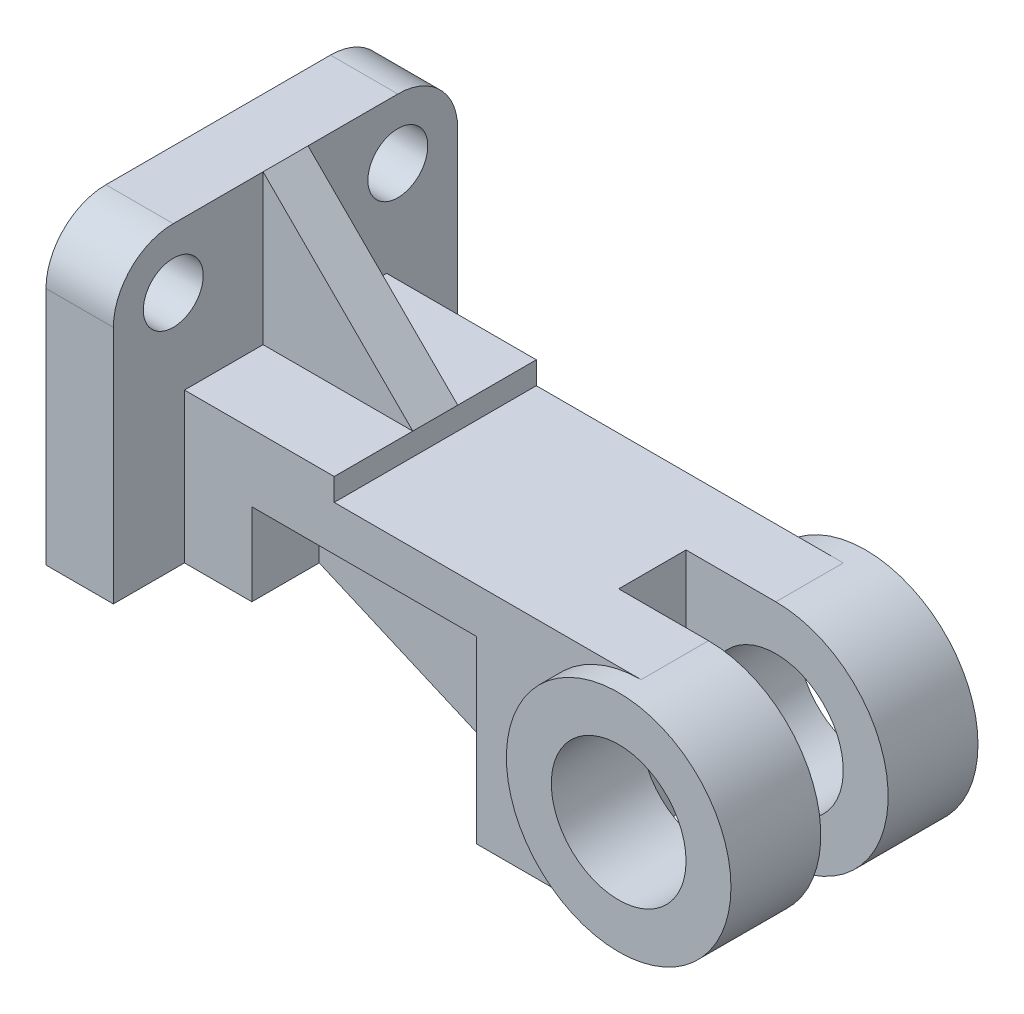
SolidWorks part; units mm, degrees
ref_plane "Front Plane" through (0, 0, 0) normal (0, 0, 1) x (1, 0, 0)
ref_plane "Top Plane" through (0, 0, 0) normal (0, 1, 0) x (1, 0, 0)
ref_plane "Right Plane" through (0, 0, 0) normal (1, 0, 0) x (0, 0, -1)
sketch "Sketch2" plane through (0, 0, 0) normal (0, 0, 1) x (1, 0, 0)
  line L0 (0, 30) -> (-82, 30)
  line L1 (-82, 30) -> (-82, 36)
  line L2 (-82, 36) -> (-122, 36)
  line L3 (-122, 36) -> (-122, -4)
  line L4 (-122, -4) -> (-104, -4)
  line L5 (-44, -30) -> (0, -30)
  line L6 (-104, -4) -> (-44, -30)
  circle A0 centre (0, 0) radius 18
  circle A1 centre (0, 0) radius 30
  dimension "D1" = 60
  dimension "D2" = 36
  dimension "D3" = 40
  dimension "D4" = 6
  dimension "D5" = 18
  dimension "D6" = 60
  dimension "D7" = 122
  dimension "D8" = 40
extrude "Boss-Extrude1" add sketch "Sketch2" along normal mid plane 54 contours A1 L0 L1 L2 L3 L4 L6 L5 | A1 A0 | A0 region at (-68.3088, 6.6382, 0) region at (20.6132, 20.6132, 0) region at (0, 0, 0)
extrude "Boss-Extrude2" add sketch "Sketch2<3>" along normal mid plane 66 contours A1
sketch "Sketch2<3>" plane through (0, 0, 0) normal (0, 0, 1) x (1, 0, 0) same geometry as "Sketch2"
extrude "Cut-Extrude1" cut sketch "Sketch2<4>" against normal blind 66 and the other way blind 66 contours A0
sketch "Sketch2<4>" plane through (0, 0, 0) normal (0, 0, 1) x (1, 0, 0) same geometry as "Sketch2"
sketch "Sketch3" plane through (0, 0, 27) normal (0, 0, 1) x (1, 0, 0)
  line L0 (-104, -4) -> (-104, 18)
  line L1 (-104, 18) -> (-44, 18)
  line L2 (-44, 18) -> (-44, -30)
  line L3 (-44, -30) -> (-104, -4)
  line L4 (0, 30) -> (-82, 30) construction
  dimension "D1" = 12
extrude "Cut-Extrude2" cut sketch "Sketch3" against normal blind 18
ref_plane "MIDPLANE" through (0, 0, 0) normal (0, 0, 1) x (1, 0, 0)
mirror "Mirror1" about plane through (0, 0, 0) normal (0, 0, 1) of "Cut-Extrude2"
sketch "Sketch4" plane through (-122, 0, 0) normal (-1, 0, 0) x (0, 0, 1)
  line L1 (-30, 76) -> (30, 76)
  line L2 (-46, 60) -> (-46, -4)
  line L3 (-46, -4) -> (46, -4)
  line L4 (46, 60) -> (46, -4)
  line L5 (27, -4) -> (-27, -4) construction
  line L6 (0, 0) -> (0, 36) construction
  line L7 (27, 36) -> (-27, 36) construction
  arc A0 (46, 60) -> (30, 76) centre (30, 60) ccw
  arc A1 (-46, 60) -> (-30, 76) centre (-30, 60) cw
  circle A2 centre (-30, 60) radius 8
  circle A3 centre (30, 60) radius 8
  point P13 (46, 76)
  dimension "D3" = 16
  dimension "D4" = 16
  dimension "D1" = 92
  dimension "D2" = 80
extrude "Boss-Extrude3" add sketch "Sketch4" along normal blind 18
sketch "Sketch5" plane through (0, 30, 0) normal (0, 1, 0) x (1, 0, 0)
  line L0 (0, 0) -> (33.7304, 0) construction
  line L1 (-24, 9) -> (49.1573, 9)
  line L2 (-24, 9) -> (-24, -9)
  line L3 (-24, -9) -> (49.1573, -9)
  line L4 (49.1573, 9) -> (49.1573, -9)
  point P4 (-24, 0)
  dimension "D1" = 18
  dimension "D2" = 24
extrude "Cut-Extrude3" cut sketch "Sketch5" against normal through all
sketch "Sketch6" plane through (0, 0, 0) normal (0, 0, 1) x (1, 0, 0)
  line L0 (-122, 60) -> (-122, 76) construction
  line L1 (-122, -4) -> (-122, 60) construction
  line L2 (-82, 36) -> (-122, 36) construction
  line L3 (-122, 60) -> (-122, 76)
  line L4 (-122, 36) -> (-122, 60)
  line L5 (-82, 36) -> (-122, 36)
  line L6 (-122, 76) -> (-82, 36)
extrude "Boss-Extrude4" add sketch "Sketch6" along normal mid plane 12
